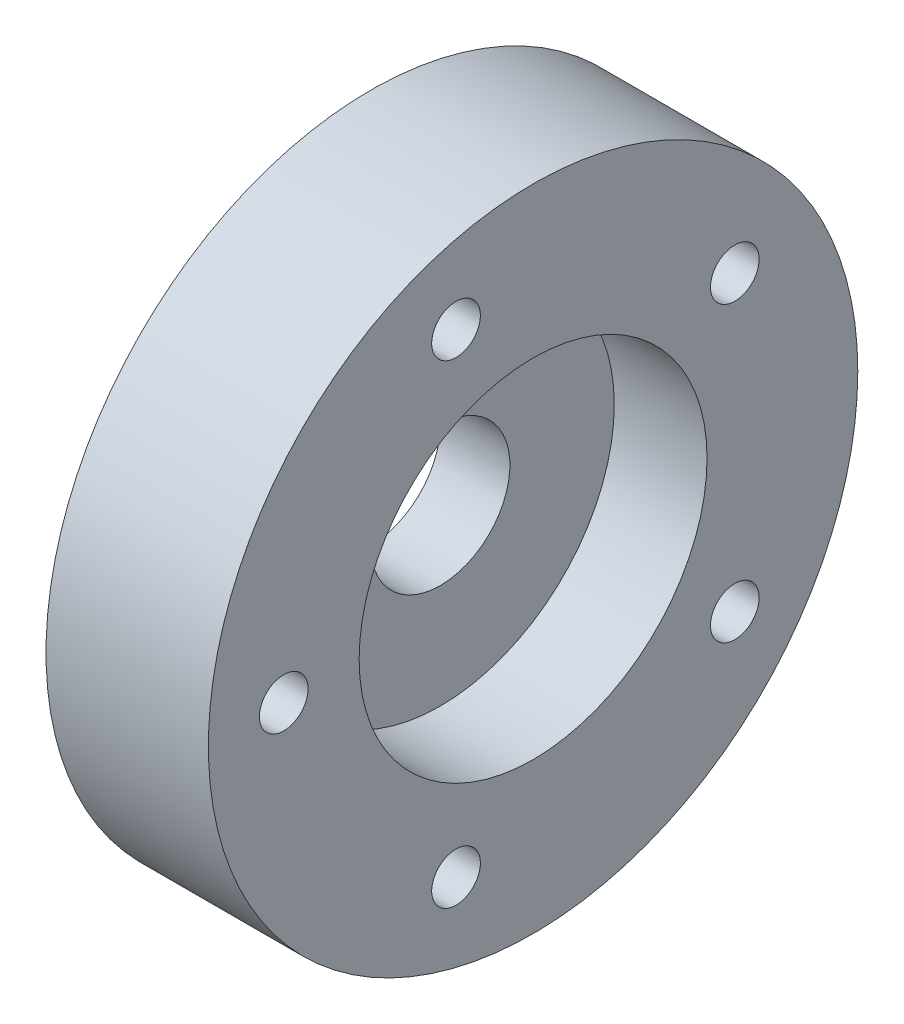
SolidWorks part; units mm, degrees
material "6061-T6 (SS)"
ref_plane "Front Plane" through (0, 0, 0) normal (1, 0, 0) x (0, 1, 0)
ref_plane "Top Plane" through (0, 0, 0) normal (0, 0, 1) x (0, 1, 0)
ref_plane "Right Plane" through (0, 0, 0) normal (0, 1, 0) x (-1, 0, 0)
sketch "Sketch1" plane through (0, 0, 0) normal (1, 0, 0) x (0, 1, 0)
  circle A0 centre (0, 0) radius 28
  dimension "D1" = 56
extrude "Boss-Extrude1" add sketch "Sketch1" along normal blind 14
sketch "Sketch2" plane through (14, 0, 0) normal (1, 0, 0) x (0, 1, 0)
  circle A0 centre (0, 0) radius 15
  dimension "D1" = 30
extrude "Cut-Extrude1" cut sketch "Sketch2" against normal blind 8
sketch "Sketch3" plane through (0, 0, 0) normal (-1, 0, 0) x (0, -1, 0)
  line L0 (0, 0) -> (0, 7.7969) construction
  line L1 (-2, 7.7969) -> (2, 7.7969)
  line L2 (-2, 7.7969) -> (-2, 5.6569)
  line L3 (2, 7.7969) -> (2, 5.6569)
  arc A0 (-2, 5.6569) -> (2, 5.6569) centre (0, 0) ccw
  point P7 (0, 7.7969)
  dimension "D1" = 12
  dimension "D2" = 4
  dimension "D3" = 2.14
extrude "Cut-Extrude2" cut sketch "Sketch3" against normal blind 16
sketch "Sketch9" plane through (14, 0, 0) normal (1, 0, 0) x (0, 1, 0)
  circle A1 centre (0, 0) radius 21.5 construction
  circle A2 centre (0, 21.5) radius 1.5
  circle A3 centre (20.4477, 6.6439) radius 1.5
  circle A4 centre (12.6374, -17.3939) radius 1.5
  circle A5 centre (-12.6374, -17.3939) radius 1.5
  circle A6 centre (-20.4477, 6.6439) radius 1.5
  point P6 (0, 0)
  point P7 (0, 0)
  point P15 (0, 0)
  dimension "D1" = 3
  dimension "D2" = 43
  dimension "D3" = 5
hole_wizard "M5x0.8 Tapped Hole1" positions "3DSketch5" profile "Sketch10" tap size "M5x0.8" standard "ANSI Metric"
sketch3d "3DSketch5"
  point P0 (14, -20.4477, 6.6439)
  point P3 (14, 0, 21.5)
  point P6 (14, -12.6374, -17.3939)
  point P9 (14, 12.6374, -17.3939)
  point P12 (14, 20.4477, 6.6439)
sketch "Sketch10" plane through (14, -20.4477, 6.6439) normal (0, 1, 0) x (0, 0, -1)
  line L0 (0, 0) -> (0, 9.2618)
  line L1 (0, 9.2618) -> (2.1, 8)
  line L2 (2.1, 8) -> (2.1, 0)
  line L5 (2.1, 0) -> (0, 0)
  line L10 (0, 9.2618) -> (-2.1, 8) construction
  line L11 (0, -6.35) -> (0, 107.95) construction
  dimension "Tap Drill Dia." = 4.2
  dimension "Tap Drill Depth" = 8
  dimension "Drill Angle" = 118
